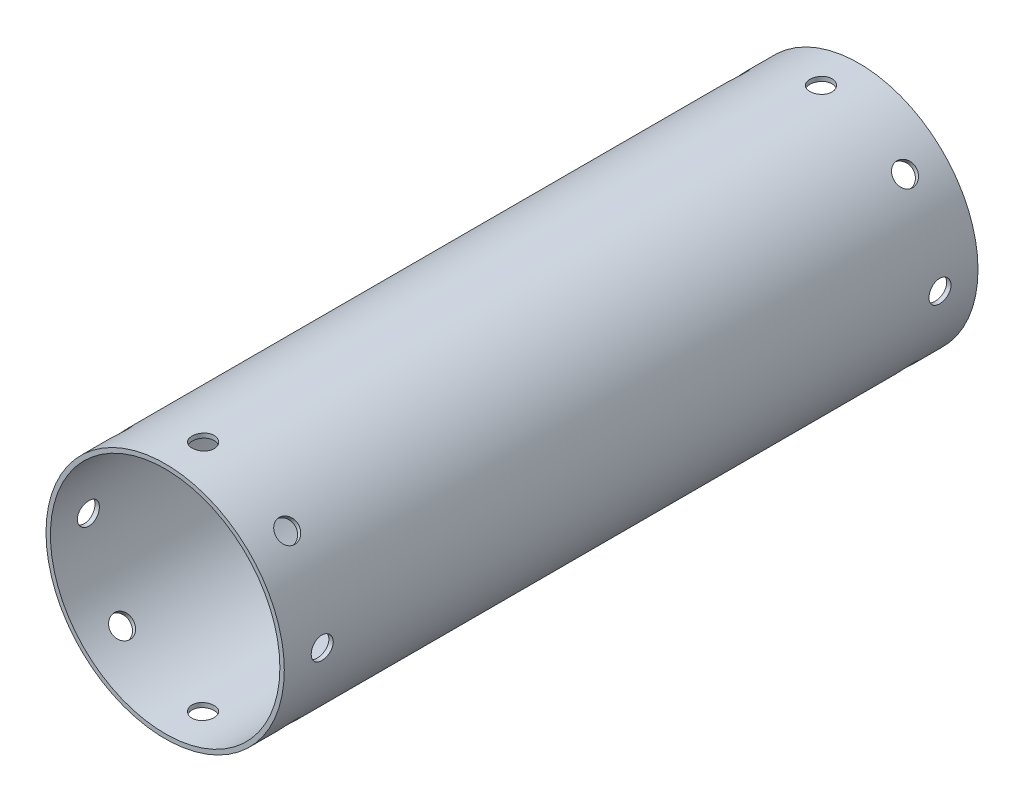
SolidWorks part; units mm, degrees
ref_plane "Front Plane" through (0, 0, 0) normal (0, 0, 1) x (1, 0, 0)
ref_plane "Top Plane" through (0, 0, 0) normal (0, 1, 0) x (1, 0, 0)
ref_plane "Right Plane" through (0, 0, 0) normal (1, 0, 0) x (0, 0, -1)
sketch "Sketch1" plane through (0, 0, 0) normal (0, 0, 1) x (1, 0, 0)
  circle A0 centre (0, 0) radius 27
  circle A1 centre (0, 0) radius 26
  dimension "D1" = 54
  dimension "D2" = 52
extrude "Boss-Extrude1" add sketch "Sketch1" along normal blind 157.2
sketch "Sketch2" plane through (0, 0, 0) normal (0, 1, 0) x (1, 0, 0)
  line L0 (27, 0) -> (-27, 0) construction
  circle A0 centre (0, -8.6) radius 2.5
  dimension "D1" = 5
  dimension "D2" = 8.6
extrude "Cut-Extrude1" cut sketch "Sketch2" against normal up to next and the other way blind 1
sketch "Sketch3" plane through (0, 0, 0) normal (0, 1, 0) x (1, 0, 0)
  line L0 (0, -149.7653) -> (0, 20.6247) construction
pattern_linear "LPattern1" count 2 spacing 140 along (0, 0, 1) of "Cut-Extrude1"
pattern_circular "CirPattern2" count 8 over 360 about axis through (0, 0, 157.2) along (0, 0, -1) of "LPattern1"
